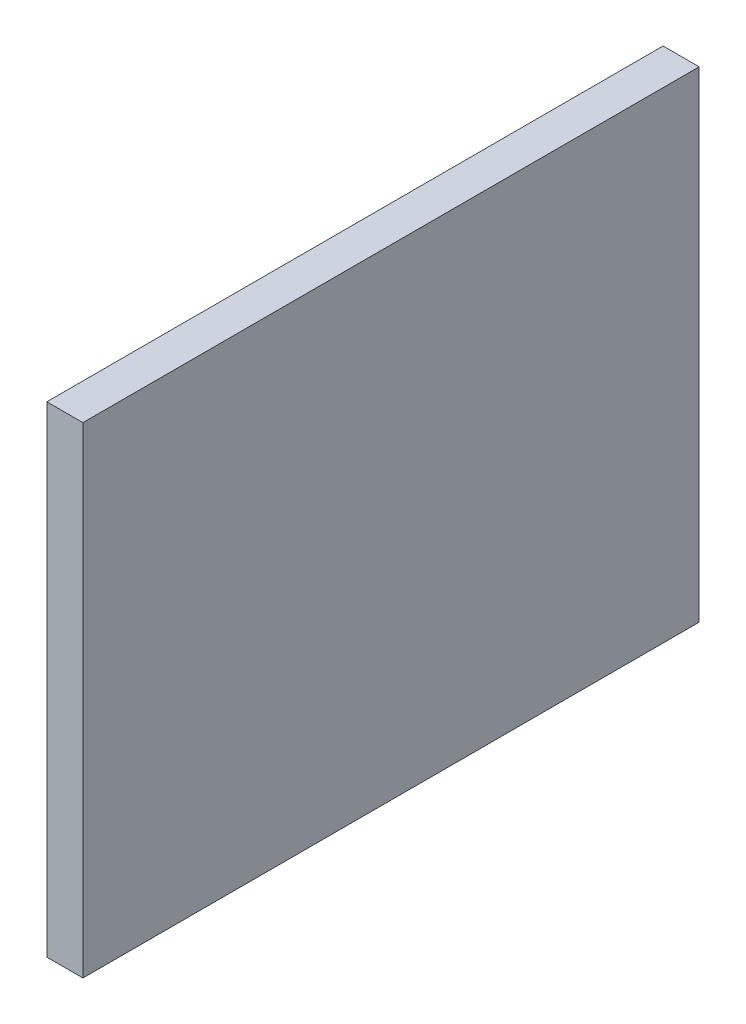
SolidWorks part; units mm, degrees
ref_plane "Front" through (0, 0, 0) normal (0, 0, 1) x (1, 0, 0)
ref_plane "Top" through (0, 0, 0) normal (0, 1, 0) x (1, 0, 0)
ref_plane "Right" through (0, 0, 0) normal (1, 0, 0) x (0, 0, -1)
sketch "Sketch1" plane through (0, 0, 0) normal (0, 1, 0) x (1, 0, 0)
  line L1 (0, 0) -> (76.2, 0)
  line L2 (0, 0) -> (0, -1355.725)
  line L3 (0, -1355.725) -> (76.2, -1355.725)
  line L4 (76.2, 0) -> (76.2, -1355.725)
  dimension "D1" = 76.2
  dimension "D2" = 1355.725
extrude "Boss-Extrude1" add sketch "Sketch1" along normal blind 1016
sketch "Sketch2" plane through (0, 0, 0) normal (-1, 0, 0) x (0, 0, 1)
  line L0 (0, 1016) -> (1355.725, 1016) construction
  line L1 (1355.725, 0) -> (1254.125, 0)
  line L2 (1355.725, 0) -> (1355.725, 1016)
  line L3 (1355.725, 1016) -> (1254.125, 1016)
  line L4 (1254.125, 0) -> (1254.125, 1016)
  dimension "D1" = 101.6
extrude "Cut-Extrude1" [suppressed] cut sketch "Sketch2" against normal through all
sketch "Sketch3" plane through (0, 0, 0) normal (-1, 0, 0) x (0, 0, 1)
  line L0 (0, 1016) -> (1355.725, 1016) construction
  line L1 (1355.725, 0) -> (1301.75, 0)
  line L2 (1355.725, 0) -> (1355.725, 1016)
  line L3 (1355.725, 1016) -> (1301.75, 1016)
  line L4 (1301.75, 0) -> (1301.75, 1016)
  line L5 (0, 1016) -> (0, 0) construction
  dimension "D1" = 1301.75
extrude "Cut-Extrude2" cut sketch "Sketch3" against normal through all
